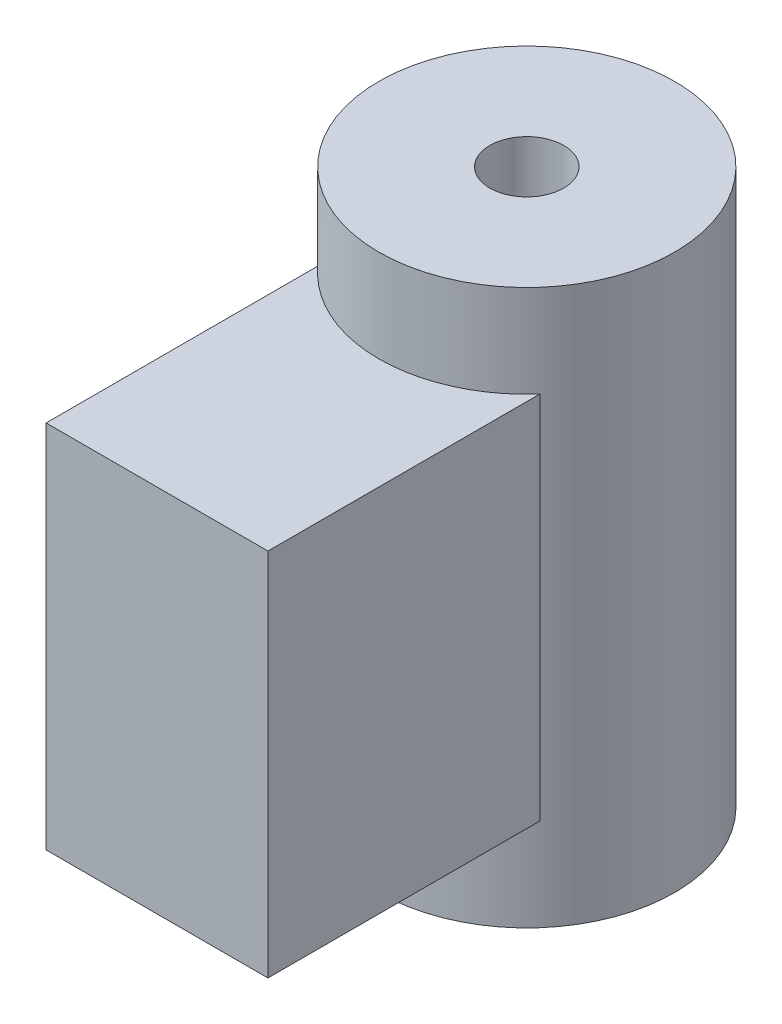
SolidWorks part; units mm, degrees
ref_plane "Спереди" through (0, 0, 0) normal (0, 0, 1) x (1, 0, 0)
ref_plane "Сверху" through (0, 0, 0) normal (0, 1, 0) x (1, 0, 0)
ref_plane "Справа" through (0, 0, 0) normal (1, 0, 0) x (0, 0, -1)
sketch "Эскиз1" plane through (0, 0, 0) normal (0, 1, 0) x (1, 0, 0)
  circle A0 centre (0, 0) radius 1
  circle A1 centre (0, 0) radius 4
  dimension "D1" = 2
  dimension "D2" = 8
extrude "Бобышка-Вытянуть1" add sketch "Эскиз1" along normal mid plane 15
sketch "Эскиз3" plane through (0, 0, 0) normal (0, 1, 0) x (1, 0, 0)
  line L0 (-3, -2.6458) -> (-3, -10)
  line L1 (-3, -10) -> (3, -10)
  line L2 (3, -10) -> (3, -2.6458)
  line L3 (0, 4.8824) -> (0, -11.2993) construction
  circle A0 centre (0, 0) radius 4 construction
  circle A2 centre (0, 0) radius 4
  arc A3 (-3, -2.6458) -> (3, -2.6458) centre (0, 0) ccw
  dimension "D1" = 6
  dimension "D2" = 10
  dimension "D3" = 0
extrude "Бобышка-Вытянуть2" add sketch "Эскиз3" along normal mid plane 10
